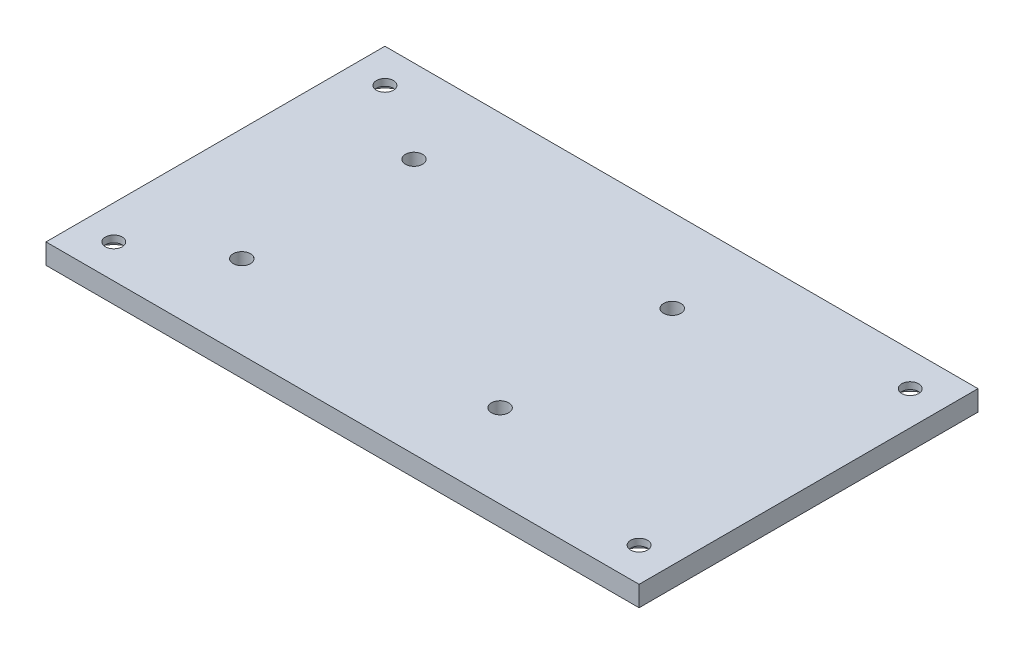
SolidWorks part; units mm, degrees
ref_plane "Front Plane" through (0, 0, 0) normal (0, 0, 1) x (1, 0, 0)
ref_plane "Top Plane" through (0, 0, 0) normal (0, 1, 0) x (1, 0, 0)
ref_plane "Right Plane" through (0, 0, 0) normal (1, 0, 0) x (0, 0, -1)
sketch "Sketch1" plane through (0, 0, 0) normal (0, 1, 0) x (1, 0, 0)
  line L0 (-55, 0) -> (55, 0) construction
  line L1 (-87.5, 50) -> (87.5, 50)
  line L2 (-87.5, 50) -> (-87.5, -50)
  line L3 (-87.5, -50) -> (87.5, -50)
  line L4 (87.5, 50) -> (87.5, -50)
  line L5 (-87.5, 50) -> (87.5, -50) construction
  line L6 (-87.5, -50) -> (87.5, 50) construction
  line L7 (0, -55) -> (0, 55) construction
  circle A0 centre (-77.5, -40) radius 2.5
  circle A1 centre (-77.5, 40) radius 2.5
  circle A2 centre (77.5, 40) radius 2.5
  circle A3 centre (77.5, -40) radius 2.5
  circle A4 centre (-63.5, 25.4) radius 2.5 construction
  circle A5 centre (-63.5, -25.4) radius 2.5 construction
  circle A6 centre (63.5, -25.4) radius 2.5 construction
  circle A7 centre (63.5, 25.4) radius 2.5 construction
  point P0 (0, 0)
  dimension "D3" = 5
  dimension "D1" = 100
  dimension "D2" = 175
  dimension "D4" = 40
  dimension "D5" = 77.5
  dimension "D6" = 25.4
  dimension "D7" = 63.5
extrude "Boss-Extrude1" add sketch "Sketch1" along normal blind 6
sketch "Sketch2" plane through (0, 6, 0) normal (0, 1, 0) x (1, 0, 0)
  line L0 (-55, 0) -> (55, 0) construction
  line L1 (0, -55) -> (0, 55) construction
  line L2 (-87.5, 50) -> (-87.5, -50) construction
  line L3 (-87.5, 0) -> (87.5, 0) construction
  line L4 (87.5, -50) -> (87.5, 50) construction
  circle A0 centre (-77.5, 40) radius 5
  circle A1 centre (-77.5, -40) radius 5
  circle A2 centre (77.5, -40) radius 5
  circle A3 centre (77.5, 40) radius 5
  circle A8 centre (21.88, -25.4) radius 2.555
  circle A9 centre (-54.32, -25.4) radius 2.555
  circle A10 centre (21.88, 25.4) radius 2.555
  circle A11 centre (-54.32, 25.4) radius 2.555
  point P23 (0, 0)
  point P24 (0, 0)
  dimension "D1" = 10
  dimension "D3" = 65.62
  dimension "D5" = 5.11
  dimension "D2" = 5.11
  dimension "D4" = 76.2
  dimension "D6" = 25.4
  dimension "D7" = 50.8
extrude "Cut-Extrude1" cut sketch "Sketch2" against normal through all contours A9 | A11 | A8 | A10
sketch "Sketch3" plane through (0, 0, 0) normal (0, 1, 0) x (1, 0, 0)
  line L0 (0, -3.3) -> (0, 3.3) construction
  line L1 (-3.3, 0) -> (3.3, 0) construction
  circle A0 centre (-77.5, 40) radius 7.5
  circle A1 centre (77.5, 40) radius 7.5
  circle A2 centre (77.5, -40) radius 7.5
  circle A3 centre (-77.5, -40) radius 7.5
  dimension "D1" = 15
extrude "Cut-Extrude2" cut sketch "Sketch3" along normal blind 4
